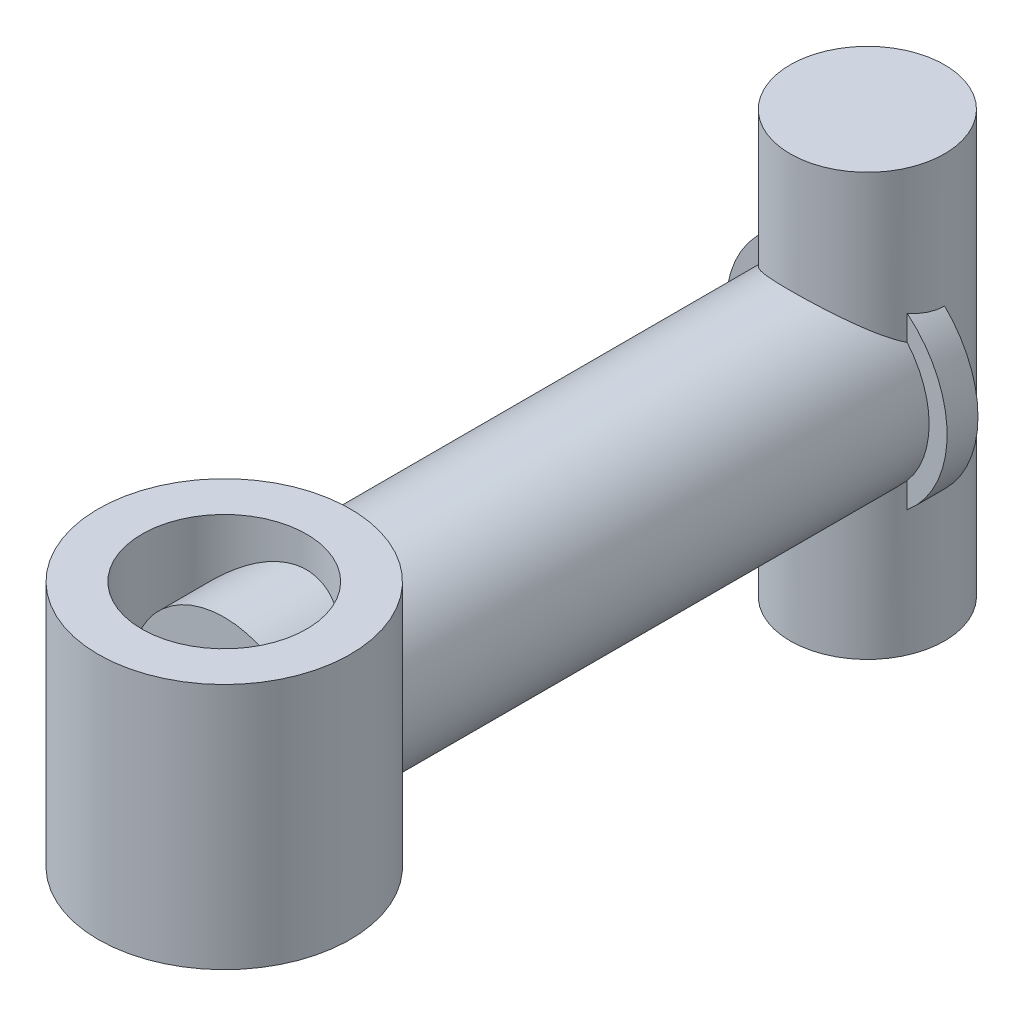
SolidWorks part; units mm, degrees
ref_plane "前视基准面" through (0, 0, 0) normal (0, 0, 1) x (1, 0, 0)
ref_plane "上视基准面" through (0, 0, 0) normal (0, 1, 0) x (1, 0, 0)
ref_plane "右视基准面" through (0, 0, 0) normal (1, 0, 0) x (0, 0, -1)
other "Configuration Table"
sketch "草图1" plane through (0, 0, 0) normal (0, 1, 0) x (1, 0, 0)
  circle A0 centre (0, 0) radius 30
extrude "凸台-拉伸1" add sketch "草图1" along normal blind 82 and the other way blind 82
sketch "草图2" plane through (0, 0, 0) normal (0, 0, 1) x (1, 0, 0)
  circle A0 centre (0, 0) radius 43
extrude "凸台-拉伸2" add sketch "草图2" along normal blind 12
sketch "草图3" plane through (0, 0, 0) normal (0, 0, 1) x (1, 0, 0)
  circle A0 centre (0, 0) radius 36
extrude "凸台-拉伸3" add sketch "草图3" along normal blind 250
sketch "草图4" plane through (0, 0, 0) normal (0, 0, 1) x (1, 0, 0)
  line L1 (36, -12) -> (40, -12)
  line L2 (36, -12) -> (36, 12)
  line L3 (36, 12) -> (40, 12)
  line L4 (40, -12) -> (40, 12)
  line L5 (36, -12) -> (40, 12) construction
  line L6 (36, 12) -> (40, -12) construction
  line L7 (-40, -12) -> (-36, -12)
  line L8 (-40, -12) -> (-40, 12)
  line L9 (-40, 12) -> (-36, 12)
  line L10 (-36, -12) -> (-36, 12)
  line L11 (-40, -12) -> (-36, 12) construction
  line L12 (-40, 12) -> (-36, -12) construction
  point P0 (38, 0)
  point P5 (-38, 0)
sketch "草图5" plane through (0, 0, 0) normal (0, 1, 0) x (1, 0, 0)
  circle A0 centre (0, -250) radius 32
  circle A1 centre (0, -250) radius 49
extrude "凸台-拉伸5" add sketch "草图5" along normal blind 48 and the other way blind 48
